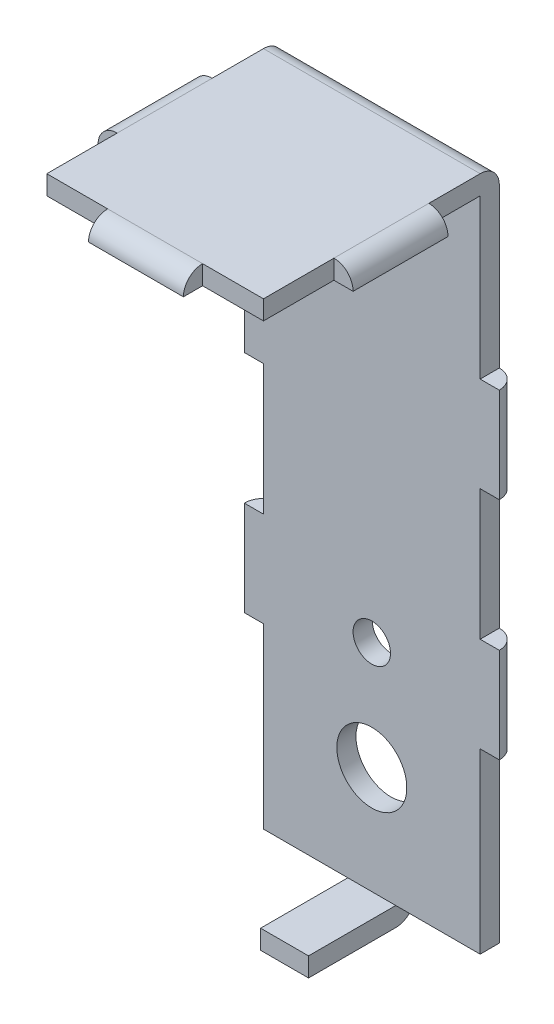
SolidWorks part; units mm, degrees
material "ABS"
ref_plane "Front Plane" through (0, 0, 0) normal (0, 0, 1) x (1, 0, 0)
ref_plane "Top Plane" through (0, 0, 0) normal (0, 1, 0) x (1, 0, 0)
ref_plane "Right Plane" through (0, 0, 0) normal (1, 0, 0) x (0, 0, -1)
sketch "Sketch1" plane through (0, 0, 0) normal (0, 0, 1) x (1, 0, 0)
  line L1 (-11.3, -35.25) -> (11.3, -35.25)
  line L2 (-11.3, -35.25) -> (-11.3, 35.25)
  line L3 (-11.3, 35.25) -> (11.3, 35.25)
  line L4 (11.3, -35.25) -> (11.3, 35.25)
  line L5 (-11.3, -35.25) -> (11.3, 35.25) construction
  line L6 (-11.3, 35.25) -> (11.3, -35.25) construction
  point P0 (0, 0)
  dimension "D1" = 70.5
  dimension "D2" = 22.6
extrude "Boss-Extrude1" add sketch "Sketch1" along normal blind 2
sketch "Sketch2" plane through (0, 0, 2) normal (0, 0, 1) x (1, 0, 0)
  line L0 (-11.3, 35.25) -> (-11.3, -35.25) construction
  line L1 (-11.3, 33.25) -> (11.3, 33.25)
  line L2 (-11.3, 33.25) -> (-11.3, 35.25)
  line L3 (-11.3, 35.25) -> (11.3, 35.25)
  line L4 (11.3, 33.25) -> (11.3, 35.25)
  line L5 (-11.3, 33.25) -> (11.3, 35.25) construction
  line L6 (-11.3, 35.25) -> (11.3, 33.25) construction
  point P0 (0, 34.25)
  dimension "D1" = 2
extrude "Boss-Extrude2" add sketch "Sketch2" along normal blind 22.6
sketch "Sketch3" plane through (0, 35.25, 0) normal (0, 1, 0) x (1, 0, 0)
  line L0 (-11.3, -7.35) -> (-11.3, -17.25)
  line L5 (-11.3, -24.6) -> (-11.3, 0) construction
  line L10 (0, 0) -> (0, -24.6) construction
  line L11 (11.3, -24.6) -> (-11.3, -24.6) construction
  line L18 (-13.3, -17.25) -> (-13.3, -7.35)
  line L19 (-11.3, -12.3) -> (-13.3, -7.35) construction
  line L20 (-11.3, -12.3) -> (-13.3, -17.25) construction
  line L21 (-13.3, -7.35) -> (-11.3, -7.35)
  line L22 (-13.3, -17.25) -> (-11.3, -17.25)
  line L23 (11.3, -12.3) -> (13.3, -17.25) construction
  line L24 (11.3, -12.3) -> (13.3, -7.35) construction
  line L25 (13.3, -17.25) -> (11.3, -17.25)
  line L26 (13.3, -7.35) -> (11.3, -7.35)
  line L27 (13.3, -17.25) -> (13.3, -7.35)
  line L28 (11.3, -7.35) -> (11.3, -17.25)
  line L29 (-4.95, -26.6) -> (-4.95, -24.6)
  line L30 (-4.95, -26.6) -> (4.95, -26.6)
  line L34 (-4.95, -26.6) -> (0, -24.6) construction
  line L35 (0, -24.6) -> (4.95, -26.6) construction
  line L36 (4.95, -26.6) -> (4.95, -24.6)
  line L37 (-4.95, -24.6) -> (4.95, -24.6)
  point P0 (-11.3, -12.3)
  point P9 (-13.3, -12.3)
  point P19 (11.3, -12.3)
  point P26 (0, -26.6)
  dimension "D1" = 9.9
  dimension "D2" = 2
  dimension "D3" = 12.3
  dimension "D4" = 9.9
  dimension "D5" = 2
extrude "Boss-Extrude3" add sketch "Sketch3" against normal blind 2
sketch "Sketch4" plane through (0, 0, 2) normal (0, 0, 1) x (1, 0, 0)
  line L0 (0, 33.25) -> (0, -35.25) construction
  line L1 (-4.95, 33.25) -> (4.95, 33.25) construction
  line L2 (-11.3, -35.25) -> (11.3, -35.25) construction
  line L3 (11.3, -35.25) -> (11.3, 33.25) construction
  line L7 (13.3, 6.8) -> (13.3, 16.7)
  line L8 (11.3, 11.75) -> (13.3, 16.7) construction
  line L9 (11.3, 11.75) -> (13.3, 6.8) construction
  line L10 (13.3, 16.7) -> (11.3, 16.7)
  line L14 (13.3, -16.7) -> (13.3, -6.8)
  line L15 (11.3, -11.75) -> (13.3, -6.8) construction
  line L16 (11.3, -11.75) -> (13.3, -16.7) construction
  line L17 (13.3, 6.8) -> (11.3, 6.8)
  line L18 (13.3, -6.8) -> (11.3, -6.8)
  line L19 (13.3, -16.7) -> (11.3, -16.7)
  line L20 (11.3, 16.7) -> (11.3, 6.8)
  line L21 (11.3, -6.8) -> (11.3, -16.7)
  line L22 (-11.3, -11.75) -> (-13.3, -16.7) construction
  line L23 (-11.3, -11.75) -> (-13.3, -6.8) construction
  line L24 (-11.3, 11.75) -> (-13.3, 6.8) construction
  line L25 (-11.3, 11.75) -> (-13.3, 16.7) construction
  line L26 (-11.3, -6.8) -> (-11.3, -16.7)
  line L27 (-11.3, 16.7) -> (-11.3, 6.8)
  line L28 (-13.3, -16.7) -> (-11.3, -16.7)
  line L29 (-13.3, -6.8) -> (-11.3, -6.8)
  line L30 (-13.3, 6.8) -> (-11.3, 6.8)
  line L31 (-13.3, -16.7) -> (-13.3, -6.8)
  line L32 (-13.3, 16.7) -> (-11.3, 16.7)
  line L33 (-13.3, 6.8) -> (-13.3, 16.7)
  point P6 (11.3, 11.75)
  point P13 (11.3, -11.75)
  point P21 (13.3, -11.75)
  point P23 (13.3, 11.75)
  point P34 (-11.3, -11.75)
  point P35 (-11.3, 11.75)
  dimension "D1" = 9.9
  dimension "D2" = 9.9
  dimension "D3" = 2
  dimension "D4" = 2
  dimension "D5" = 23.5
  dimension "D6" = 23.5
extrude "Boss-Extrude4" add sketch "Sketch4" against normal blind 2
fillet "Fillet1" radius 2 8 edges at (0, 35.25, 0) (13.3, 35.25, 12.3) (0, 35.25, 26.6) (-13.3, 35.25, 12.3) (13.3, 11.75, 0) (13.3, -11.75, 0) (-13.3, -11.75, 0) (-13.3, 11.75, 0)
sketch "Sketch5" plane through (0, 0, 0) normal (0, 0, -1) x (-1, 0, 0)
  line L0 (11.3, -35.25) -> (-11.3, -35.25) construction
  line L1 (2.5, -35.25) -> (-2.5, -35.25)
  line L2 (2.5, -35.25) -> (2.5, -37.25)
  line L3 (2.5, -37.25) -> (-2.5, -37.25)
  line L4 (-2.5, -35.25) -> (-2.5, -37.25)
  point P6 (0, -35.25)
  point P7 (0, -37.25)
  dimension "D1" = 2
  dimension "D2" = 5
extrude "Boss-Extrude5" add sketch "Sketch5" against normal blind 11.1
fillet "Fillet2" radius 2 1 edges at (0, -37.25, 0)
sketch "Sketch6" plane through (0, 0, 0) normal (0, 0, -1) x (-1, 0, 0)
  line L0 (11.3, -35.25) -> (2.5, -35.25) construction
  line L1 (-2.5, -35.25) -> (-11.3, -35.25) construction
  circle A0 centre (0, -24.05) radius 3.65
  circle A1 centre (0, -12.75) radius 1.95
  dimension "D2" = 7.3
  dimension "D4" = 3.9
  dimension "D1" = 11.2
  dimension "D3" = 22.5
extrude "Cut-Extrude1" cut sketch "Sketch6" against normal up to surface (2 mm away) up to face at (0, -3.3864, 2)
